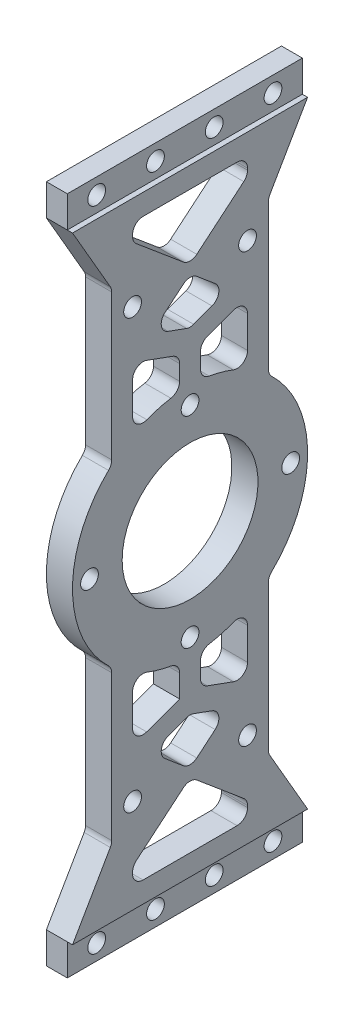
SolidWorks part; units mm, degrees
material "Сплав 2024"
ref_plane "Спереди" through (0, 0, 0) normal (0, 0, 1) x (1, 0, 0)
ref_plane "Сверху" through (0, 0, 0) normal (0, 1, 0) x (1, 0, 0)
ref_plane "Справа" through (0, 0, 0) normal (1, 0, 0) x (0, 0, -1)
sketch "Эскиз1" plane through (0, 0, 0) normal (0, 1, 0) x (1, 0, 0)
  line L1 (0, 0) -> (5, 0)
  line L2 (0, 0) -> (0, -30)
  line L3 (0, -30) -> (5, -30)
  line L4 (5, 0) -> (5, -30)
  dimension "D1" = 5
  dimension "D2" = 30
extrude "Бобышка-Вытянуть1" add sketch "Эскиз1" along normal blind 130
sketch "Эскиз2" plane through (0, 0, 0) normal (-1, 0, 0) x (0, 0, 1)
  line L0 (30, 65) -> (0, 65) construction
  line L1 (30, 130) -> (30, 0) construction
  line L2 (0, 130) -> (0, 0) construction
  line L3 (15, 130) -> (15, 0) construction
  line L4 (0, 130) -> (30, 130) construction
  line L5 (0, 0) -> (30, 0) construction
  circle A0 centre (15, 65) radius 22.5
  dimension "D1" = 45
extrude "Бобышка-Вытянуть2" add sketch "Эскиз2" against normal up to surface (5 mm away) up to face at (5, 65, 15)
sketch "Эскиз3" plane through (0, 0, 0) normal (-1, 0, 0) x (0, 0, 1)
  circle A0 centre (15, 65) radius 13
  dimension "D1" = 26
extrude "Вырез-Вытянуть1" cut sketch "Эскиз3" against normal through all
sketch "Эскиз4" plane through (5, 0, 0) normal (-1, 0, 0) x (0, 0, 1)
  line L0 (15, 87.5) -> (15, 42.5) construction
  line L1 (15, 130) -> (15, 0) construction
  line L2 (37.5, 65) -> (-7.5, 65) construction
  circle A0 centre (15, 65) radius 19.25 construction
  circle A1 centre (15, 65) radius 22.5 construction
  dimension "D1" = 38.5
hole_wizard "Отверстие с зазором M33" positions "Эскиз6" profile "Эскиз5" hole size "M3" standard "Ansi Metric" end condition through all
sketch "Эскиз6" plane through (5, -25.0247, 7.2629) normal (-1, 0, 0) x (0, 0, 1)
  line L0 (7.7371, 112.5247) -> (7.7371, 67.5247) construction
  line L1 (30.2371, 90.0247) -> (-14.7629, 90.0247) construction
  circle A0 centre (7.7371, 90.0247) radius 19.25 construction
  point P0 (7.7371, 109.2747)
  point P6 (-11.5129, 90.0247)
  point P10 (7.7371, 70.7747)
  point P12 (26.9871, 90.0247)
sketch "Эскиз5" plane through (5, 84.25, 15) normal (0, 1, 0) x (0, 0, -1)
  line L0 (0, 0) -> (0, 5)
  line L1 (0, 5) -> (1.7, 5)
  line L2 (1.7, 5) -> (1.7, 0)
  line L5 (1.7, 0) -> (0, 0)
  line L11 (0, -6.35) -> (0, 107.95) construction
  dimension "Диаметр сквозного отверстия" = 3.4
  dimension "Глубина сквозного отверстия" = 5
sketch "Эскиз8" plane through (5, 0, 0) normal (1, 0, 0) x (0, 0, -1)
  line L0 (-15, 130) -> (-15, 0) construction
  line L1 (-30, 130) -> (0, 130) construction
  line L2 (-30, 0) -> (0, 0) construction
  line L3 (19.447, 65) -> (-49.447, 65) construction
  line L4 (0, 130) -> (0, 81.7705) construction
  line L5 (-26, 106) -> (-4, 106) construction
  line L6 (-26, 106) -> (-26, 24) construction
  line L7 (-26, 24) -> (-4, 24) construction
  line L8 (-4, 106) -> (-4, 24) construction
  line L9 (-26, 106) -> (-4, 24) construction
  line L10 (-26, 24) -> (-4, 106) construction
  point P8 (-15, 65)
  point P9 (-15, 65)
  dimension "D1" = 4
  dimension "D2" = 82
hole_wizard "Отверстие с зазором M32" positions "Эскиз10" profile "Эскиз9" hole size "M3" standard "Ansi Metric" end condition through all
sketch "Эскиз10" plane through (5, 0, 0) normal (1, 0, 0) x (0, 0, -1)
  point P0 (-26, 106)
  point P3 (-4, 106)
  point P6 (-4, 24)
  point P9 (-26, 24)
sketch "Эскиз9" plane through (5, 106, 26) normal (0, 1, 0) x (0, 0, -1)
  line L0 (0, 0) -> (0, 5)
  line L1 (0, 5) -> (1.7, 5)
  line L2 (1.7, 5) -> (1.7, 0)
  line L5 (1.7, 0) -> (0, 0)
  line L11 (0, -6.35) -> (0, 107.95) construction
  dimension "Диаметр сквозного отверстия" = 3.4
  dimension "Глубина сквозного отверстия" = 5
sketch "Эскиз11" plane through (5, 0, 0) normal (1, 0, 0) x (0, 0, -1)
  line L0 (-15, 130) -> (-15, 0) construction
  line L1 (-30, 130) -> (0, 130) construction
  line L2 (-30, 0) -> (0, 0) construction
  line L3 (-37.5, 124) -> (-30, 111.0096)
  line L4 (-37.5, 124) -> (7.5, 124) construction
  line L5 (-37.5, 124) -> (-37.5, 130)
  line L6 (-37.5, 130) -> (7.5, 130)
  line L7 (7.5, 124) -> (7.5, 130)
  line L8 (-37.5, 124) -> (7.5, 130) construction
  line L9 (-37.5, 130) -> (7.5, 124) construction
  line L10 (-30, 130) -> (-30, 81.7705) construction
  line L11 (-30, 111.0096) -> (0, 111.0096)
  line L12 (0, 130) -> (0, 81.7705) construction
  line L13 (0, 111.0096) -> (7.5, 124)
  line L14 (-37.5, 127) -> (7.5, 127) construction
  line L15 (-31.875, 130) -> (-31.875, 124) construction
  line L16 (-26.25, 130) -> (-26.25, 124) construction
  line L17 (-20.625, 130) -> (-20.625, 124) construction
  line L18 (-15, 130) -> (-15, 124) construction
  line L19 (-15, 65) -> (-5.455, 65) construction
  line L20 (-15, 0) -> (-15, 6) construction
  line L21 (-20.625, 0) -> (-20.625, 6) construction
  line L22 (-26.25, 0) -> (-26.25, 6) construction
  line L23 (-31.875, 0) -> (-31.875, 6) construction
  line L24 (-37.5, 3) -> (7.5, 3) construction
  line L25 (-37.5, 0) -> (7.5, 6) construction
  line L26 (-37.5, 6) -> (7.5, 0) construction
  line L27 (-37.5, 6) -> (7.5, 6) construction
  line L28 (0, 18.9904) -> (7.5, 6)
  line L29 (-30, 18.9904) -> (0, 18.9904)
  line L30 (7.5, 6) -> (7.5, 0)
  line L31 (-37.5, 0) -> (7.5, 0)
  line L32 (-37.5, 6) -> (-37.5, 0)
  line L33 (-37.5, 6) -> (-30, 18.9904)
  line L34 (-9.375, 130) -> (-9.375, 124) construction
  line L35 (-3.75, 130) -> (-3.75, 124) construction
  line L36 (1.875, 130) -> (1.875, 124) construction
  line L37 (-9.375, 0) -> (-9.375, 6) construction
  line L38 (-3.75, 0) -> (-3.75, 6) construction
  line L39 (1.875, 0) -> (1.875, 6) construction
  point P6 (-15, 127)
  point P45 (-15, 3)
  dimension "D1" = 6
  dimension "D2" = 45
  dimension "D3" = 120
  dimension "D4" = 5.625
  dimension "D5" = 5.625
  dimension "D6" = 5.625
  dimension "D7" = 5.625
  dimension "D8" = 5.625
  dimension "D9" = 5.625
  dimension "D10" = 5.625
extrude "Бобышка-Вытянуть3" add sketch "Эскиз11" against normal up to surface (5 mm away) up to face at (0, 106, 24.3)
hole_wizard "Отверстие с зазором M31" positions "Эскиз13" profile "Эскиз12" hole size "M3" standard "Ansi Metric" end condition through all
sketch "Эскиз13" plane through (5, 0, 0) normal (1, 0, 0) x (0, 0, -1)
  line L0 (-31.875, 130) -> (-31.875, 124) construction
  line L4 (-31.875, 0) -> (-31.875, 6) construction
  line L8 (1.875, 130) -> (1.875, 124) construction
  line L9 (-9.375, 130) -> (-9.375, 124) construction
  line L10 (-20.625, 130) -> (-20.625, 124) construction
  line L11 (1.875, 0) -> (1.875, 6) construction
  line L12 (-9.375, 0) -> (-9.375, 6) construction
  line L13 (-20.625, 0) -> (-20.625, 6) construction
  point P0 (-31.875, 127)
  point P4 (-20.625, 127)
  point P8 (-9.375, 127)
  point P12 (1.875, 127)
  point P16 (-31.875, 3)
  point P20 (-20.625, 3)
  point P24 (-9.375, 3)
  point P28 (1.875, 3)
sketch "Эскиз12" plane through (5, 127, 31.875) normal (0, 1, 0) x (0, 0, -1)
  line L0 (0, 0) -> (0, 5)
  line L1 (0, 5) -> (1.7, 5)
  line L2 (1.7, 5) -> (1.7, 0)
  line L5 (1.7, 0) -> (0, 0)
  line L11 (0, -6.35) -> (0, 107.95) construction
  dimension "Диаметр сквозного отверстия" = 3.4
  dimension "Глубина сквозного отверстия" = 5
sketch "Эскиз14" plane through (5, 0, 0) normal (1, 0, 0) x (0, 0, -1)
  line L1 (-37.5, 130) -> (7.5, 130)
  line L2 (-37.5, 130) -> (-37.5, 124)
  line L3 (-37.5, 124) -> (7.5, 124)
  line L4 (7.5, 130) -> (7.5, 124)
  line L5 (-37.5, 0) -> (7.5, 0)
  line L6 (-37.5, 0) -> (-37.5, 6)
  line L7 (-37.5, 6) -> (7.5, 6)
  line L8 (7.5, 0) -> (7.5, 6)
extrude "Вырез-Вытянуть2" cut sketch "Эскиз14" against normal blind 1
sketch "Эскиз15" plane through (5, 0, 0) normal (1, 0, 0) x (0, 0, -1)
  line L0 (-26, 0) -> (-26, 130) construction
  line L1 (-37.5, 0) -> (7.5, 0) construction
  line L2 (7.5, 130) -> (-37.5, 130) construction
  line L3 (-4, 130) -> (-4, 0) construction
  line L4 (-30, 48.2295) -> (-30, 18.9904) construction
  line L5 (0, 48.2295) -> (0, 18.9904) construction
  line L6 (-15, 65) -> (0, 65) construction
  line L7 (-17, 42.5891) -> (-17, 36.5058)
  line L8 (-13, 42.5891) -> (-13, 36.5058)
  line L9 (-15, 130) -> (-15, 0) construction
  line L10 (-26, 24) -> (-4, 24) construction
  line L11 (-17, 36.5058) -> (-26, 33.2301)
  line L12 (-26, 33.2301) -> (-26, 45.3722)
  line L13 (-13, 36.5058) -> (-4, 33.2301)
  line L14 (-4, 33.2301) -> (-4, 45.3722)
  line L15 (-15, 32.9771) -> (-22.4618, 30.2612)
  line L16 (-22.4618, 30.2612) -> (-15, 24)
  line L17 (-15, 24) -> (-7.5382, 30.2612)
  line L18 (-7.5382, 30.2612) -> (-15, 32.9771)
  line L19 (-26, 33.2301) -> (-15, 24) construction
  line L20 (-4, 33.2301) -> (-15, 24) construction
  line L21 (-30, 22.5) -> (0, 22.5) construction
  line L22 (-15, 22.5) -> (-26, 13.2699) construction
  line L23 (-15, 22.5) -> (-4, 13.2699) construction
  line L24 (-4, 13.2699) -> (-26, 13.2699) construction
  line L25 (-15, 22.5) -> (-26, 13.2699)
  line L26 (-35.1906, 10) -> (5.1906, 10) construction
  line L27 (-30, 18.9904) -> (-37.5, 6) construction
  line L28 (7.5, 6) -> (0, 18.9904) construction
  line L29 (7.5, 6) -> (-37.5, 6) construction
  line L30 (-26, 13.2699) -> (-26, 10)
  line L31 (-26, 10) -> (-4, 10)
  line L32 (-4, 10) -> (-4, 13.2699)
  line L33 (-4, 13.2699) -> (-15, 22.5)
  line L34 (-13, 87.4109) -> (-13, 93.4942)
  line L35 (-13, 93.4942) -> (-4, 96.7699)
  line L36 (-4, 96.7699) -> (-4, 84.6278)
  line L37 (-26, 96.7699) -> (-26, 84.6278)
  line L38 (-17, 93.4942) -> (-26, 96.7699)
  line L39 (-17, 87.4109) -> (-17, 93.4942)
  line L40 (-7.5382, 99.7388) -> (-15, 97.0229)
  line L41 (-15, 97.0229) -> (-22.4618, 99.7388)
  line L42 (-22.4618, 99.7388) -> (-15, 106)
  line L43 (-15, 106) -> (-7.5382, 99.7388)
  line L44 (-4, 120) -> (-4, 116.7301)
  line L45 (-4, 116.7301) -> (-15, 107.5)
  line L46 (-15, 107.5) -> (-26, 116.7301)
  line L47 (-26, 116.7301) -> (-26, 120)
  line L48 (-26, 120) -> (-4, 120)
  circle A0 centre (-15, 65) radius 22.5 construction
  arc A1 (-26, 45.3722) -> (-17, 42.5891) centre (-15, 65) ccw
  arc A2 (-13, 42.5891) -> (-4, 45.3722) centre (-15, 65) ccw
  arc A3 (-13, 87.4109) -> (-4, 84.6278) centre (-15, 65) cw
  arc A4 (-26, 84.6278) -> (-17, 87.4109) centre (-15, 65) cw
  point P22 (-26, 45.3722)
  point P23 (-4, 45.3722)
  point P40 (-15, 22.5)
  dimension "D5" = 110
  dimension "D1" = 4
  dimension "D2" = 4
  dimension "D3" = 4
  dimension "D4" = 2
  dimension "D6" = 100
  dimension "D7" = 4
  dimension "D8" = 1.5
  dimension "D9" = 4
  dimension "D10" = 100
extrude "Вырез-Вытянуть3" cut sketch "Эскиз15" against normal up to next
fillet "Скругление1" radius 2 8 edges at (2.5, 111.0096, 0) (2.5, 81.7705, 0) (2.5, 48.2295, 0) (2.5, 18.9904, 0) (2.5, 18.9904, 30) (2.5, 48.2295, 30) (2.5, 81.7705, 30) (2.5, 111.0096, 30)
fillet "Скругление2" radius 2 33 edges at (2.5, 13.2699, 4) (2.5, 10, 4) (2.5, 13.2699, 26) (2.5, 10, 26) (2.5, 24, 15) (2.5, 33.2301, 4) (2.5, 30.2612, 7.5382) (2.5, 30.2612, 22.4618) (2.5, 36.5058, 13) (2.5, 33.2301, 26) (2.5, 45.3722, 4) (2.5, 42.5891, 17) (2.5, 22.5, 15) (2.5, 32.9771, 15) (2.5, 45.3722, 26) (2.5, 42.5891, 13) (2.5, 84.6278, 26) (2.5, 96.7699, 26) (2.5, 87.4109, 13) (2.5, 93.4942, 13) (2.5, 84.6278, 4) (2.5, 96.7699, 4) (2.5, 93.4942, 17) (2.5, 87.4109, 17) (2.5, 99.7388, 7.5382) (2.5, 97.0229, 15) (2.5, 99.7388, 22.4618) (2.5, 106, 15) (2.5, 120, 4) (2.5, 116.7301, 4) (2.5, 107.5, 15) (2.5, 116.7301, 26) (2.5, 120, 26)
equation "\"D4@Эскиз11\"=\"D2@Эскиз11\"/8"
equation "\"D5@Эскиз11\"=\"D4@Эскиз11\""
equation "\"D6@Эскиз11\"=\"D4@Эскиз11\""
equation "\"D7@Эскиз11\"=\"D4@Эскиз11\""
equation "\"D8@Эскиз11\"=\"D4@Эскиз11\""
equation "\"D9@Эскиз11\"=\"D4@Эскиз11\""
equation "\"D10@Эскиз11\"=\"D4@Эскиз11\""
